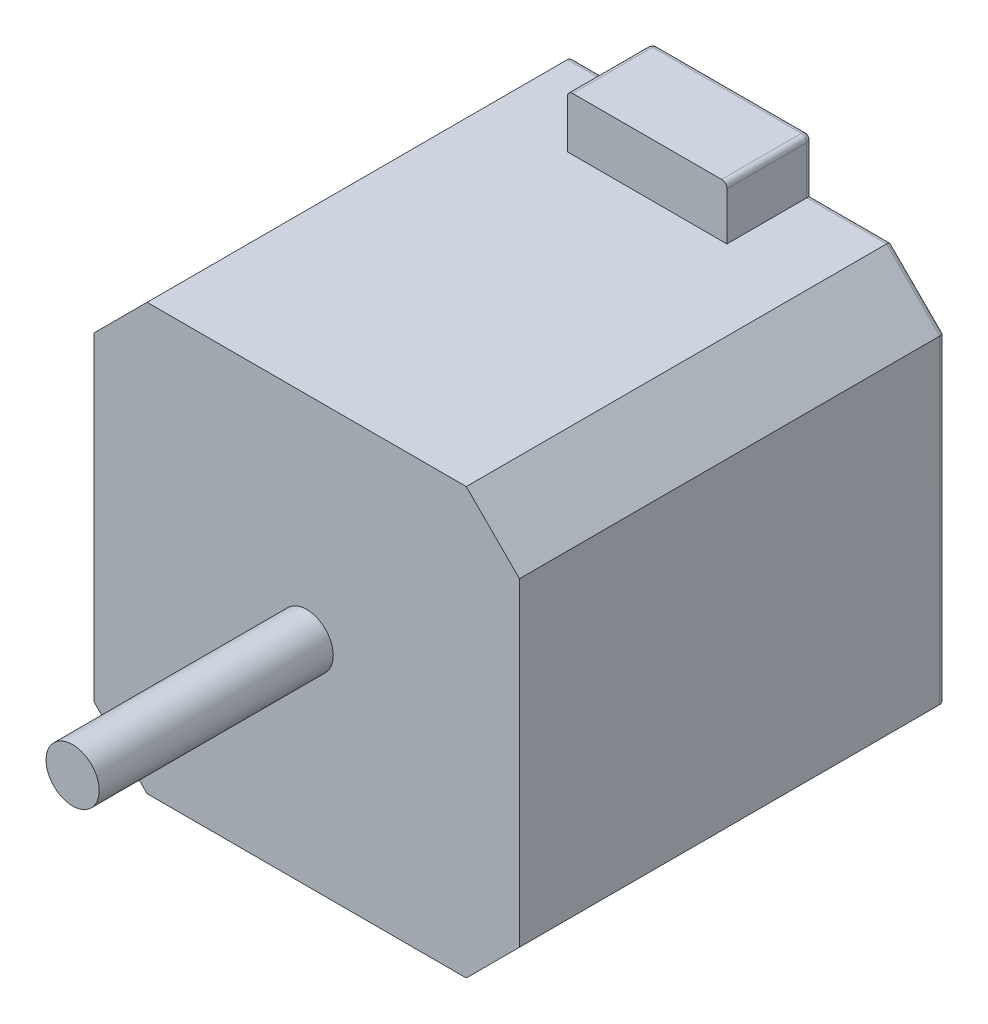
SolidWorks part; units mm, degrees
ref_plane "Front Plane" through (0, 0, 0) normal (0, 0, 1) x (1, 0, 0)
ref_plane "Top Plane" through (0, 0, 0) normal (0, 1, 0) x (1, 0, 0)
ref_plane "Right Plane" through (0, 0, 0) normal (1, 0, 0) x (0, 0, -1)
sketch "Sketch1" plane through (0, 0, 0) normal (0, 0, 1) x (1, 0, 0)
  line L1 (20, -20) -> (-20, -20)
  line L2 (20, -20) -> (20, 20)
  line L3 (20, 20) -> (-20, 20)
  line L4 (-20, -20) -> (-20, 20)
  line L5 (20, -20) -> (-20, 20) construction
  line L6 (20, 20) -> (-20, -20) construction
  point P0 (0, 0)
  dimension "D1" = 40
extrude "Boss-Extrude1" add sketch "Sketch1" along normal blind 40
chamfer "Chamfer1" distance 5 angle 45 4 edges at (-20, -20, 20) (20, -20, 20) (-20, 20, 20) (20, 20, 20)
sketch "Sketch2" plane through (0, 0, 0) normal (0, 0, 1) x (1, 0, 0)
  line L0 (0, -22) -> (0, 22) construction
  line L1 (7.5, 25) -> (-7.5, 25)
  line L2 (7.5, 25) -> (7.5, 20)
  line L3 (7.5, 20) -> (-7.5, 20)
  line L4 (-7.5, 25) -> (-7.5, 20)
  line L5 (7.5, 25) -> (-7.5, 20) construction
  line L6 (7.5, 20) -> (-7.5, 25) construction
  line L7 (15, 20) -> (-15, 20) construction
  point P0 (0, 22.5)
  dimension "D1" = 15
  dimension "D2" = 5
extrude "Boss-Extrude2" add sketch "Sketch2" along normal blind 8
fillet "Fillet1" radius 0.5 12 edges at (17.5, -17.5, 0) (20, 0, 0) (17.5, 17.5, 0) (11.25, 20, 0) (7.5, 22.5, 0) (0, 25, 0) (-7.5, 22.5, 0) (-11.25, 20, 0) (-17.5, 17.5, 0) (-20, 0, 0) (-17.5, -17.5, 0) (0, -20, 0)
fillet "Fillet2" radius 0.5 4 edges at (-7.3536, 24.8536, 0.1464) (7.3536, 24.8536, 0.1464) (-7.5, 25, 4.25) (7.5, 25, 4.25)
sketch "Sketch3" plane through (0, 0, 0) normal (0, 0, 1) x (1, 0, 0)
  circle A0 centre (0, 0) radius 2.5
  dimension "D1" = 5
extrude "Boss-Extrude3" add sketch "Sketch3" along normal blind 62
